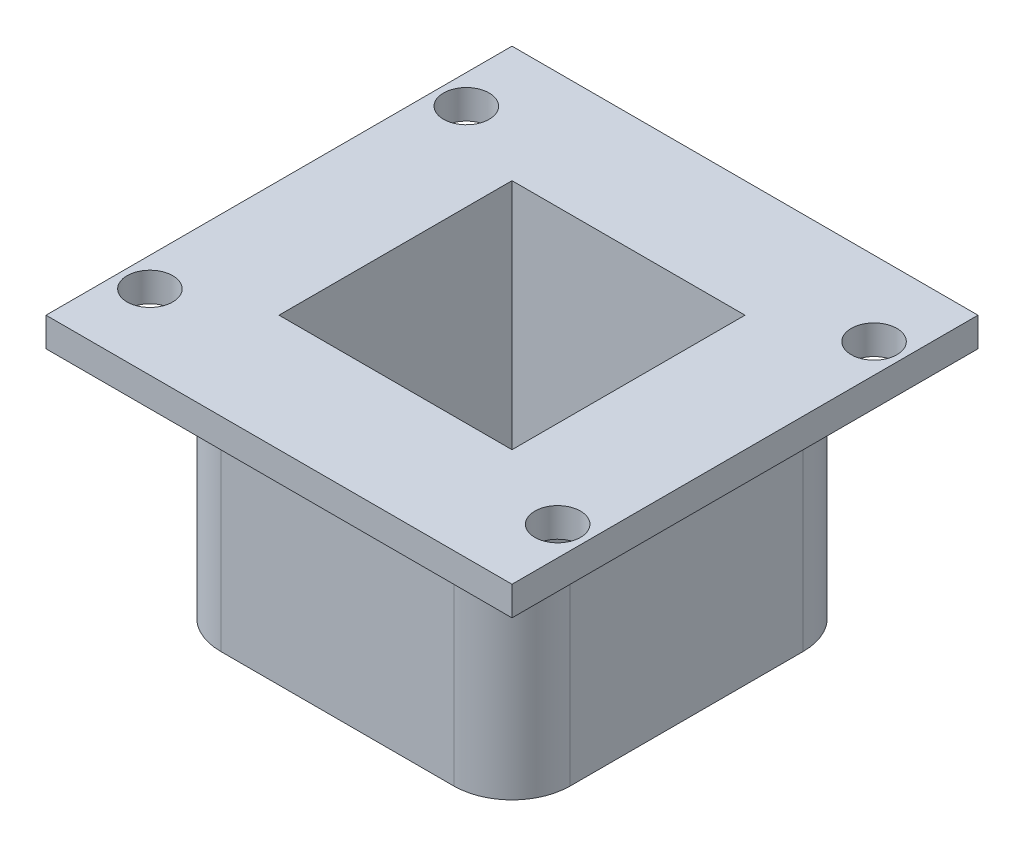
SolidWorks part; units mm, degrees
note: The reader was unsure of these and kept them because the rebuilt part matched: shared geometry of "Sketch1<3>".
ref_plane "Front" through (0, 0, 0) normal (0, 0, 1) x (1, 0, 0)
ref_plane "Top" through (0, 0, 0) normal (0, 1, 0) x (1, 0, 0)
ref_plane "Right" through (0, 0, 0) normal (1, 0, 0) x (0, 0, -1)
sketch "Sketch1" plane through (0, 0, 0) normal (0, 1, 0) x (1, 0, 0)
  line L0 (-19.05, -19.05) -> (-25.4, -25.4) construction
  line L1 (-25.4, -25.4) -> (25.4, -25.4)
  line L2 (-25.4, -25.4) -> (-25.4, 25.4)
  line L3 (-25.4, 25.4) -> (25.4, 25.4)
  line L4 (25.4, -25.4) -> (25.4, 25.4)
  line L5 (-25.4, -25.4) -> (25.4, 25.4) construction
  line L6 (-25.4, 25.4) -> (25.4, -25.4) construction
  line L7 (-19.05, -19.05) -> (19.05, -19.05)
  line L8 (-19.05, -19.05) -> (-19.05, 19.05)
  line L9 (-19.05, 19.05) -> (19.05, 19.05)
  line L10 (19.05, -19.05) -> (19.05, 19.05)
  line L11 (-19.05, -19.05) -> (19.05, 19.05) construction
  line L12 (-19.05, 19.05) -> (19.05, -19.05) construction
  line L13 (-17.1901, 17.1901) -> (-25.4, 25.4) construction
  line L14 (-25.4, 17.2466) -> (-19.05, 17.2466) construction
  line L15 (-25.4, 0) -> (25.4, 0) construction
  line L16 (0, 25.4) -> (0, -25.4) construction
  arc A1 (-19.05, 12.7) -> (-12.7, 19.05) centre (-12.7, 12.7) cw
  circle A2 centre (-22.225, 17.2466) radius 2.4892
  arc A4 (12.7, 19.05) -> (19.05, 12.7) centre (12.7, 12.7) cw
  arc A6 (19.05, -12.7) -> (12.7, -19.05) centre (12.7, -12.7) cw
  arc A8 (-12.7, -19.05) -> (-19.05, -12.7) centre (-12.7, -12.7) cw
  circle A9 centre (-17.2466, -22.225) radius 2.4892 [skipped]
  circle A10 centre (22.225, -17.2466) radius 2.4892 [skipped]
  circle A11 centre (17.2466, 22.225) radius 2.4892 [skipped]
  circle A12 centre (22.225, 17.2466) radius 2.4892
  circle A13 centre (22.225, -17.2466) radius 2.4892
  circle A14 centre (-22.225, -17.2466) radius 2.4892
  point P0 (0, 0)
  point P5 (0, 0)
  point P18 (-22.225, 17.2466)
  point P34 (0, 0)
  dimension "D3" = 6.35
  dimension "D4" = 4.9784
  dimension "D1" = 38.1
  dimension "D2" = 50.8
  dimension "D6" = 8.1534
  dimension "D5" = 4
extrude "Boss-Extrude1" add sketch "Sketch1" along normal blind 3.175
extrude "Boss-Extrude2" add sketch "Sketch1<3>" against normal blind 25.4 contours A8 L7 A6 L10 A4 L9 A1 L8
sketch "Sketch1<3>" plane through (0, 0, 0) normal (0, 1, 0) x (1, 0, 0) same geometry as "Sketch1"
sketch "Sketch2" plane through (0, 3.175, 0) normal (0, 1, 0) x (1, 0, 0)
  line L1 (-12.7, -12.7) -> (12.7, -12.7)
  line L2 (-12.7, -12.7) -> (-12.7, 12.7)
  line L3 (-12.7, 12.7) -> (12.7, 12.7)
  line L4 (12.7, -12.7) -> (12.7, 12.7)
  line L5 (-12.7, -12.7) -> (12.7, 12.7) construction
  line L6 (-12.7, 12.7) -> (12.7, -12.7) construction
  point P0 (0, 0)
  dimension "D1" = 25.4
extrude "Cut-Extrude1" cut sketch "Sketch2" against normal through all
